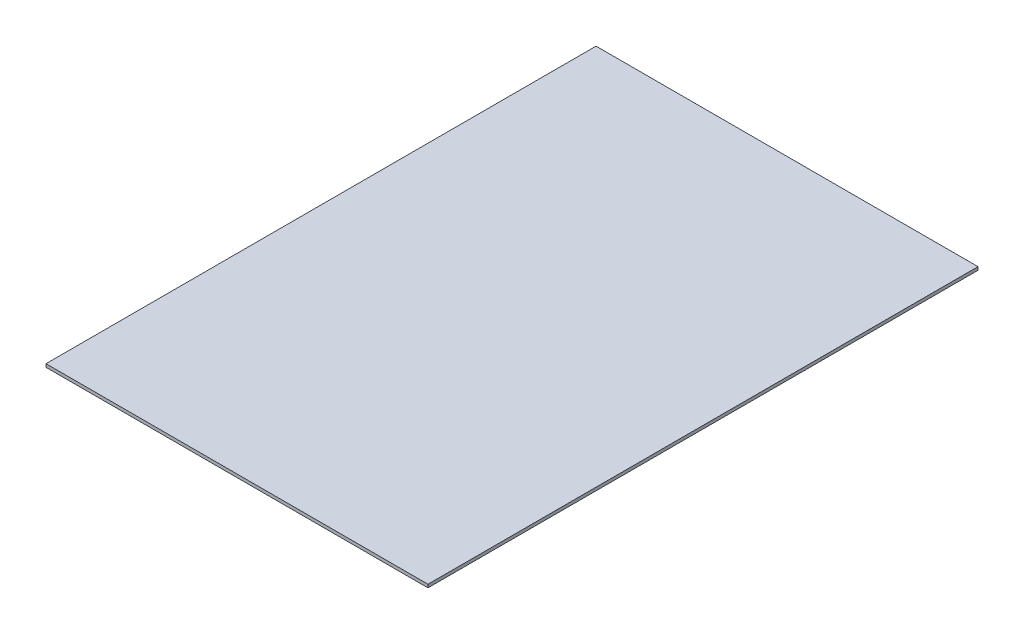
SolidWorks part; units mm, degrees
ref_plane "Front Plane" through (0, 0, 0) normal (0, 0, 1) x (1, 0, 0)
ref_plane "Top Plane" through (0, 0, 0) normal (0, 1, 0) x (1, 0, 0)
ref_plane "Right Plane" through (0, 0, 0) normal (1, 0, 0) x (0, 0, -1)
sketch "BaseSketch" plane through (0, 0, 0) normal (0, 1, 0) x (1, 0, 0)
  line L0 (30.5336, 229.9512) -> (-54.5013, 229.9512) construction
  line L1 (-139.7, -317.5) -> (139.7, -317.5)
  line L2 (-215.9, -190.5) -> (-215.9, 317.5)
  line L3 (-215.9, 317.5) -> (215.9, 317.5)
  line L4 (215.9, -190.5) -> (215.9, 317.5)
  line L5 (-215.9, -317.5) -> (215.9, 317.5) construction
  line L6 (-215.9, 317.5) -> (215.9, -317.5) construction
  line L7 (215.9, -190.5) -> (139.7, -190.5)
  line L8 (139.7, -190.5) -> (139.7, -317.5)
  line L9 (139.7, -317.5) -> (-139.7, -317.5)
  line L10 (-139.7, -317.5) -> (-139.7, -190.5)
  line L11 (-139.7, -190.5) -> (-215.9, -190.5)
  line L12 (215.9, -190.5) -> (215.9, -317.5) construction
  line L13 (215.9, -317.5) -> (139.7, -317.5) construction
  line L14 (-139.7, -317.5) -> (-215.9, -317.5) construction
  line L15 (-215.9, -317.5) -> (-215.9, -190.5) construction
  line L16 (0, -2.0955) -> (0, 2.0955) construction
  point P0 (0, 0)
  dimension "D1" = 90
extrude "Boss-Extrude1" add sketch "BaseSketch" along normal blind 3.81 contours L11 L10 L1 L8 L7 L4 L3 L2 region at (0, 0, -19.2911)
sketch "Sketch7" plane through (0, 3.81, 0) normal (0, 1, 0) x (1, 0, 0)
  line L1 (-215.9, 317.5) -> (215.9, 317.5) construction
  line L2 (-215.9, -190.5) -> (-215.9, 317.5) construction
  line L3 (-139.7, -317.5) -> (139.7, -317.5) construction
  line L4 (215.9, -190.5) -> (215.9, 317.5) construction
  line L12 (230.9, -332.5) -> (230.9, 332.5)
  line L13 (230.9, 332.5) -> (-230.9, 332.5)
  line L14 (-230.9, 332.5) -> (-230.9, -332.5)
  line L15 (-230.9, -332.5) -> (230.9, -332.5)
  dimension "D1" = 15
  dimension "D2" = 15
  dimension "D3" = 15
  dimension "D4" = 15
extrude "Boss-Extrude2" add sketch "Sketch7" against normal up to surface (3.81 mm away) up to face at (0, 0, 95.25)
